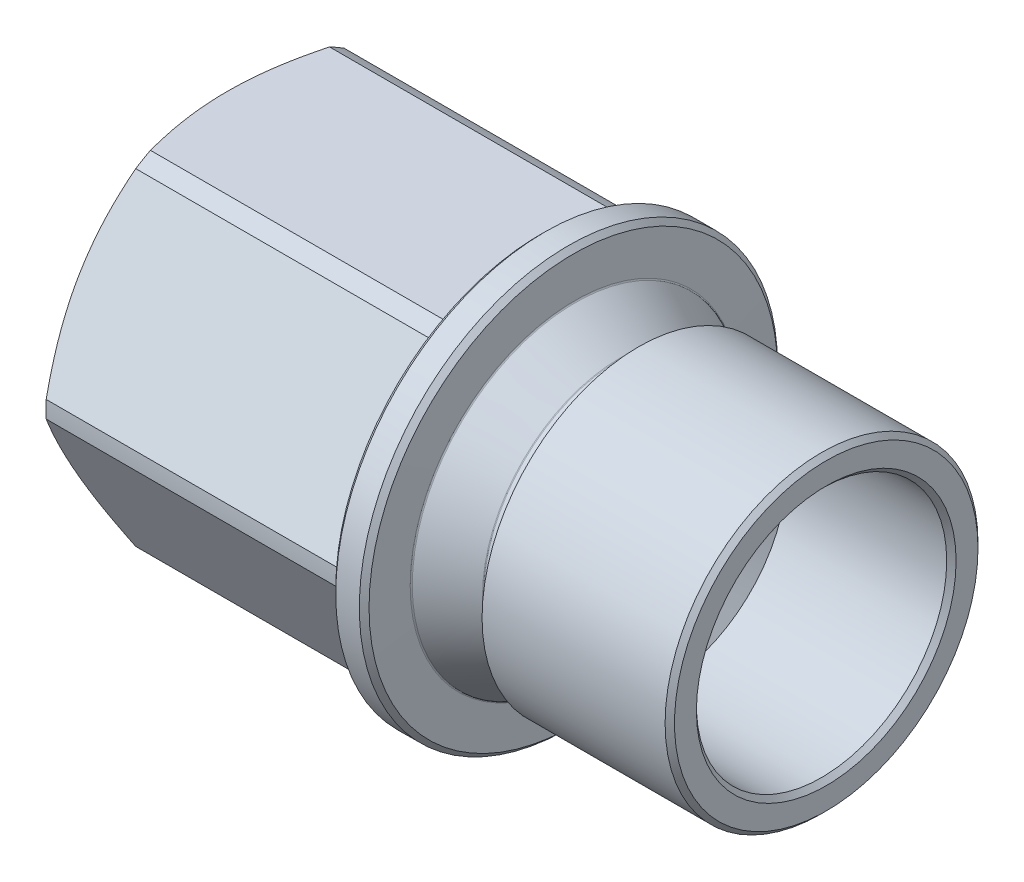
SolidWorks part; units mm, degrees
ref_plane "Piano frontale" through (0, 0, 0) normal (0, 0, 1) x (1, 0, 0)
ref_plane "Piano superiore" through (0, 0, 0) normal (0, 1, 0) x (1, 0, 0)
ref_plane "Piano destro" through (0, 0, 0) normal (1, 0, 0) x (0, 0, -1)
sketch "Schizzo1" plane through (0, 0, 0) normal (0, 0, 1) x (1, 0, 0)
  line L0 (0, 13.3696) -> (0, 0)
  line L1 (0, 0) -> (18.2824, 0)
  line L2 (18.2824, 0) -> (18.2824, 10)
  line L3 (18.2824, 10) -> (6.2824, 10)
  line L4 (6.2824, 10) -> (5.5772, 8.7785)
  line L5 (5.5772, 8.7785) -> (5.1257, 8.7785)
  line L6 (5.1257, 8.7785) -> (2.2075, 10.4633)
  line L7 (2.2075, 10.4633) -> (2.106, 13.3696)
  line L8 (2.106, 13.3696) -> (0, 13.3696)
  line L9 (0, 0) -> (18.2824, 0) construction
  dimension "D1" = 12
  dimension "D2" = 10
revolve "Rivoluzione1" add sketch "Schizzo1" angle 360 about L9 reverse direction yes
sketch "Schizzo2" plane through (0, 0, 0) normal (-1, 0, 0) x (0, 0, 1)
  line L0 (5.7236, -11) -> (-5.7236, -11)
  line L1 (-6.6645, -10.4568) -> (-12.3881, -0.5432)
  line L2 (-12.3881, 0.5432) -> (-6.6645, 10.4568)
  line L3 (-5.7236, 11) -> (5.7236, 11)
  line L4 (6.6645, 10.4568) -> (12.3881, 0.5432)
  line L5 (12.3881, -0.5432) -> (6.6645, -10.4568)
  arc A0 (6.6645, -10.4568) -> (5.7236, -11) centre (0, 0) cw
  arc A1 (-5.7236, -11) -> (-6.6645, -10.4568) centre (0, 0) cw
  arc A2 (-12.3881, -0.5432) -> (-12.3881, 0.5432) centre (0, 0) cw
  arc A3 (-6.6645, 10.4568) -> (-5.7236, 11) centre (0, 0) cw
  arc A4 (5.7236, 11) -> (6.6645, 10.4568) centre (0, 0) cw
  arc A5 (12.3881, 0.5432) -> (12.3881, -0.5432) centre (0, 0) cw
extrude "Estrusione-Estrusione1" add sketch "Schizzo2" along normal blind 20
hole_wizard "Foro Ø16.0 (16)-1" positions "Schizzo4" profile "Schizzo3" hole size "Ø16.0" standard "Ansi Metric"
sketch "Schizzo4" plane through (18.2824, 0, 0) normal (1, 0, 0) x (0, 0, -1)
  point P0 (0, 0)
sketch "Schizzo3" plane through (18.2824, 0, 0) normal (0, 1, 0) x (0, 0, -1)
  line L0 (0, 0) -> (0, 15.5)
  line L1 (0, 15.5) -> (8, 10.5)
  line L2 (8, 10.5) -> (8, 0)
  line L5 (8, 0) -> (0, 0)
  line L10 (0, 15.5) -> (-8, 10.5) construction
  line L11 (0, -6.35) -> (0, 107.95) construction
  dimension "Hole Dia." = 16
  dimension "Hole Depth" = 10.5
  dimension "Drill Angle" = 115.989
chamfer "Smusso1" distance 0.3 angle 45 3 edges at (18.2824, 0, -10) (0, 0, -13.3696) (18.2824, 0, -8)
chamfer "Smusso2" distance 1.4 angle 30 6 edges at (-20, -10.7387, -6.2) (-20, 0, -12.4) (-20, -10.7387, 6.2) (-20, 0, 12.4) (-20, 10.7387, 6.2) (-20, 10.7387, -6.2) first distance on face at (-20, 0, 0)
fillet "Raccordo1" radius 0.1 3 edges at (5.1257, 0, -8.7785) (5.5772, 0, -8.7785) (2.2075, 0, -10.4633) tangent propagation no
chamfer "Smusso3" distance 0.3 angle 45 1 edges at (2.106, 0, -13.3696) first distance on face at (0.3, 0, 13.3696)
sketch "Schizzo5" plane through (-20, 0, 0) normal (-1, 0, 0) x (0, 0, 1)
  circle A0 centre (0, 0) radius 5.05
  dimension "D1" = 10.1
extrude "Taglio-Estrusione1" cut sketch "Schizzo5" against normal blind 10 draft 1
sketch "Schizzo6" plane through (-10, 0, 0) normal (-1, 0, 0) x (0, 0, 1)
  circle A0 centre (0, 0) radius 1
  dimension "D1" = 2
extrude "Taglio-Estrusione2" cut sketch "Schizzo6" against normal blind 5
sketch "Schizzo7" plane through (-5, 0, 0) normal (-1, 0, 0) x (0, 0, 1)
  circle A0 centre (0, 0) radius 6
  dimension "D1" = 12
extrude "Taglio-Estrusione3" cut sketch "Schizzo7" against normal up to surface (11.5324 mm away)
